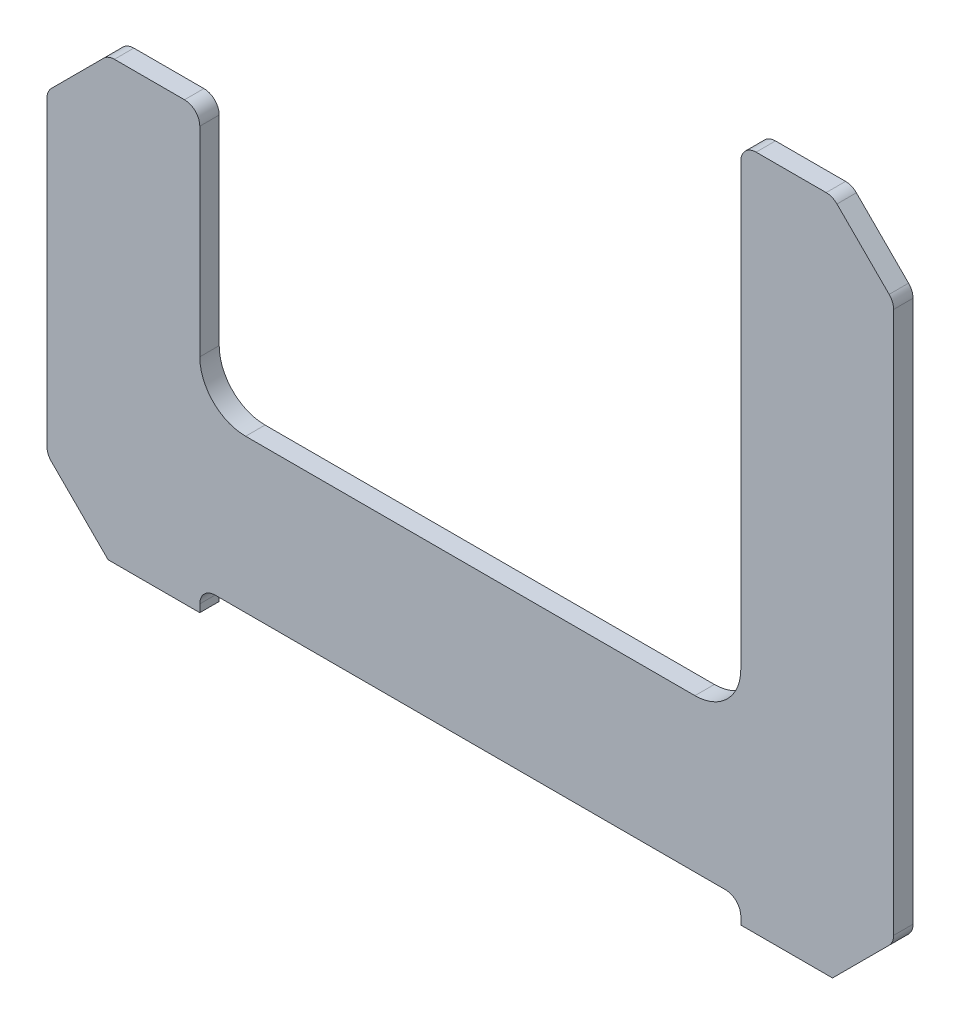
SolidWorks part; units mm, degrees
ref_plane "Front Plane" through (0, 0, 0) normal (0, 0, 1) x (1, 0, 0)
ref_plane "Top Plane" through (0, 0, 0) normal (0, 1, 0) x (1, 0, 0)
ref_plane "Right Plane" through (0, 0, 0) normal (1, 0, 0) x (0, 0, -1)
sketch "Sketch2" plane through (0, 0, 0) normal (0, 0, 1) x (1, 0, 0)
  line L0 (-138.5, 85.3385) -> (-88.5, 85.3385)
  line L1 (-88.5, 85.3385) -> (-88.5, 0)
  line L2 (-88.5, 0) -> (88.5, 0)
  line L3 (88.5, 0) -> (88.5, 164)
  line L4 (88.5, 164) -> (138.5, 164)
  line L5 (138.5, 164) -> (138.5, -57.5)
  line L6 (138.5, -57.5) -> (88.5, -57.5)
  line L7 (88.5, -57.5) -> (88.5, -50)
  line L8 (88.5, -50) -> (-88.5, -50)
  line L9 (-88.5, -50) -> (-88.5, -57.5)
  line L10 (-88.5, -57.5) -> (-138.5, -57.5)
  line L11 (-138.5, -57.5) -> (-138.5, 85.3385)
  line L12 (-33.5, 0) -> (-33.5, 124) construction
  point P10 (-33.5, 0)
  point P14 (88.5, 124)
  point P15 (-33.5, 85.3385)
  dimension "D1" = 124
  dimension "D2" = 122
  dimension "D3" = 55
  dimension "D4" = 40
  dimension "D5" = 50
  dimension "D6" = 50
  dimension "D7" = 7.5
extrude "Boss-Extrude1" add sketch "Sketch2" along normal blind 3.175 and the other way blind 3.175
chamfer "Chamfer1" distance 20 angle 45 4 edges at (-138.5, -57.5, 0) (138.5, -57.5, 0) (138.5, 164, 0) (-138.5, 85.3385, 0)
fillet "Fillet1" radius 15 2 edges at (88.5, 0, 0) (-88.5, 0, 0)
fillet "Fillet2" radius 5 10 edges at (138.5, -37.5, 0) (88.5, -50, 0) (-88.5, -50, 0) (-138.5, -37.5, 0) (-138.5, 65.3385, 0) (-118.5, 85.3385, 0) (-88.5, 85.3385, 0) (138.5, 144, 0) (118.5, 164, 0) (88.5, 164, 0)
sketch "Sketch3" plane through (0, 0, 3.175) normal (0, 0, 1) x (1, 0, 0)
  line L0 (-94.6381, 69.9757) -> (-94.6381, 14.7992)
  line L1 (-94.6381, 14.7992) -> (-97.8131, 14.7992)
  line L2 (-97.8131, 14.7992) -> (-97.8131, 69.9757)
  line L3 (-97.8131, 69.9757) -> (-94.6381, 69.9757)
  line L4 (-127.4635, 65.4691) -> (-114.3536, 78.579)
  line L5 (-114.3536, 78.579) -> (-112.1085, 76.3339)
  line L6 (-112.1085, 76.3339) -> (-125.2184, 63.2241)
  line L7 (-125.2184, 63.2241) -> (-127.4635, 65.4691)
  line L8 (-129.3392, 54.7846) -> (-126.1642, 54.7846)
  line L9 (-126.1642, 54.7846) -> (-126.1642, -28.3138)
  line L10 (-126.1642, -28.3138) -> (-129.3392, -28.3138)
  line L11 (-129.3392, -28.3138) -> (-129.3392, 54.7846)
  line L12 (-127.4635, -37.1329) -> (-125.2184, -34.8879)
  line L13 (-125.2184, -34.8879) -> (-110.9382, -49.1681)
  line L14 (-110.9382, -49.1681) -> (-113.1832, -51.4132)
  line L15 (-113.1832, -51.4132) -> (-127.4635, -37.1329)
  line L16 (-67.7784, -44.3183) -> (-67.7784, -41.1433)
  line L17 (-67.7784, -41.1433) -> (53.0181, -41.1433)
  line L18 (53.0181, -41.1433) -> (53.0181, -44.3183)
  line L19 (53.0181, -44.3183) -> (-67.7784, -44.3183)
  line L20 (114.9313, -49.5303) -> (117.1763, -51.7753)
  line L21 (117.1763, -51.7753) -> (131.7883, -37.1634)
  line L22 (131.7883, -37.1634) -> (129.5432, -34.9183)
  line L23 (129.5432, -34.9183) -> (114.9313, -49.5303)
  line L24 (-67.7784, -4.1746) -> (-67.7784, -7.3496)
  line L25 (-67.7784, -7.3496) -> (63.5847, -7.3496)
  line L26 (63.5847, -7.3496) -> (63.5847, -4.1746)
  line L27 (63.5847, -4.1746) -> (-67.7784, -4.1746)
  line L28 (92.7516, 20.9162) -> (91.2159, 151.9937)
  line L29 (91.2159, 151.9937) -> (94.3909, 151.9937)
  line L30 (94.3909, 151.9937) -> (95.9266, 20.9162)
  line L31 (95.9266, 20.9162) -> (92.7516, 20.9162)
  line L32 (96.8341, 161.8762) -> (96.8341, 158.7012)
  line L33 (96.8341, 158.7012) -> (112.5649, 158.7012)
  line L34 (112.5649, 158.7012) -> (112.5649, 161.8762)
  line L35 (112.5649, 161.8762) -> (96.8341, 161.8762)
  line L37 (117.7781, 156.4535) -> (120.0231, 158.6985)
  line L38 (120.0231, 158.6985) -> (133.8694, 144.8523)
  line L39 (133.8694, 144.8523) -> (131.6243, 142.6072)
  line L40 (131.6243, 142.6072) -> (117.7781, 156.4535)
  line L41 (129.9213, 134.1701) -> (133.0963, 134.1701)
  line L42 (133.0963, 134.1701) -> (133.0963, -24.961)
  line L43 (133.0963, -24.961) -> (129.9213, -24.961)
  line L44 (129.9213, -24.961) -> (129.9213, 134.1701)
  line L45 (118.5, -57.5) -> (137.0355, -38.9645) construction
  line L46 (-137.0355, -38.9645) -> (-118.5, -57.5) construction
  line L47 (-119.9645, 83.874) -> (-137.0355, 66.8029) construction
  line L48 (137.0355, 145.4645) -> (119.9645, 162.5355) construction
  dimension "D1" = 3.175
extrude "Cut-Extrude1" [suppressed] cut sketch "Sketch3" against normal through all
equation "\"dX\"= 122mm"
equation "\"dY\"= 124mm"
equation "\"hmotor\"= 50mm"
equation "\"D1@Sketch2\"=\"dY\""
equation "\"D2@Sketch2\"=\"dX\""
equation "\"D5@Sketch2\"=\"hmotor\""
equation "\"D6@Sketch2\"=\"hmotor\""
equation "\"t_wood\"= 0.25in"
equation "\"D1@Boss-Extrude1\"=\"t_wood\"/2"
equation "\"D2@Boss-Extrude1\"=\"t_wood\"/2"
equation "\"D1@Sketch3\"=\"t_wood\"/2"
equation "\"D1@Sketch4\"=\"t_wood\"/2"
